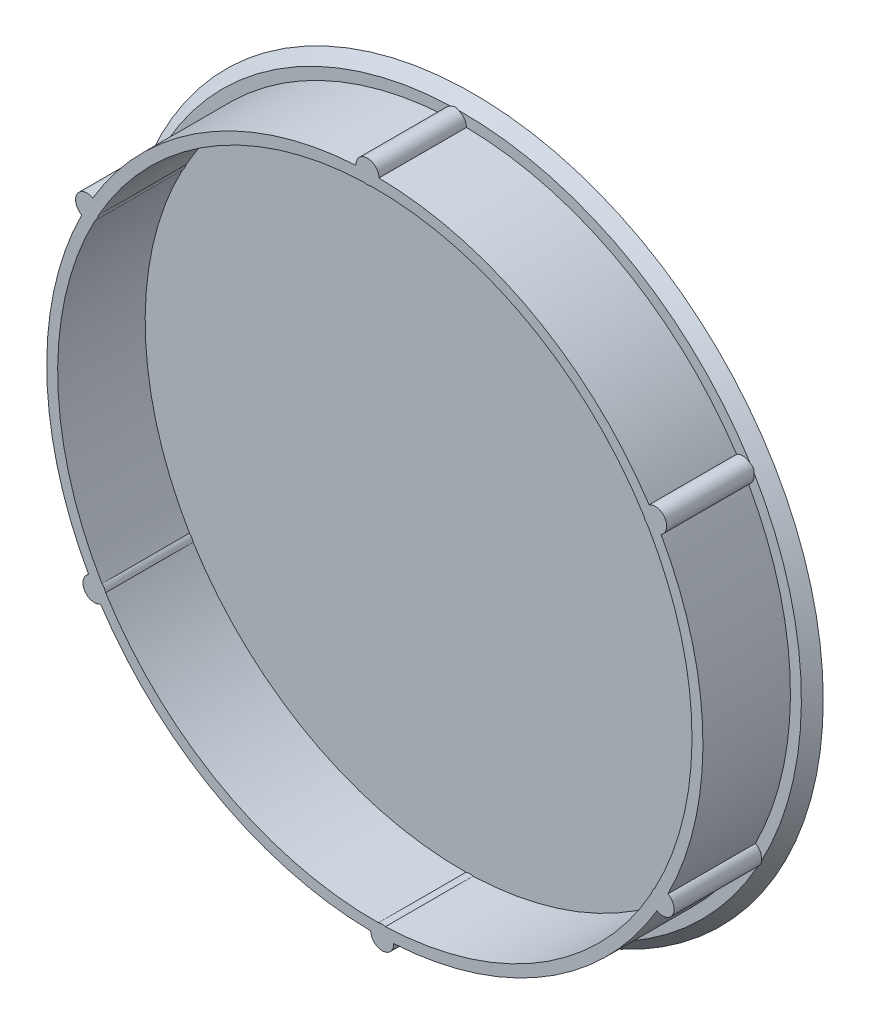
SolidWorks part; units mm, degrees
ref_plane "Спереди" through (0, 0, 0) normal (0, 0, 1) x (1, 0, 0)
ref_plane "Сверху" through (0, 0, 0) normal (0, 1, 0) x (1, 0, 0)
ref_plane "Справа" through (0, 0, 0) normal (1, 0, 0) x (0, 0, -1)
other "Configuration Table"
sketch "Эскиз1" plane through (0, 0, 0) normal (0, 1, 0) x (1, 0, 0)
  line L0 (-39.0124, 8.1896) -> (-39.0124, 9.1896)
  line L1 (-39.0124, 9.1896) -> (-6.0124, 9.1896)
  line L2 (-6.0124, 9.1896) -> (-6.0124, 8.1896)
  line L3 (-6.0124, 8.1896) -> (-35.0124, 8.1896)
  line L4 (-35.0124, 8.1896) -> (-35.0124, 0.1896)
  line L5 (-35.0124, 0.1896) -> (-36.0124, 0.1896)
  line L6 (-36.0124, 0.1896) -> (-36.0124, 8.1896)
  line L7 (-36.0124, 8.1896) -> (-39.0124, 8.1896)
  dimension "D1" = 8
  dimension "D2" = 1
  dimension "D3" = 8
  dimension "D4" = 33
  dimension "D5" = 1
  dimension "D6" = 30
revolve "Повернуть1" add sketch "Эскиз1" angle 360 about L2
sketch "Эскиз2" plane through (0, 0, -0.1896) normal (0, 0, 1) x (1, 0, 0)
  circle A0 centre (-6.6874, 29.9924) radius 1.0519
  circle A1 centre (-6.0124, 0) radius 30
  circle A2 centre (-6.0124, 0) radius 30
  dimension "D1" = 0
extrude "Бобышка-Вытянуть1" add sketch "Эскиз2" against normal up to surface (8 mm away) contours A0 up to face at (-36.0124, 0, -8.1896)
pattern_circular "Круговой массив1" count 6 every 60 about axis through (-6.0124, 0, -0.1896) along (0, 0, -1) of "Бобышка-Вытянуть1"
chamfer "Фаска1" distance 2 angle 45 1 edges at (-39.0124, 0, -8.1896)
